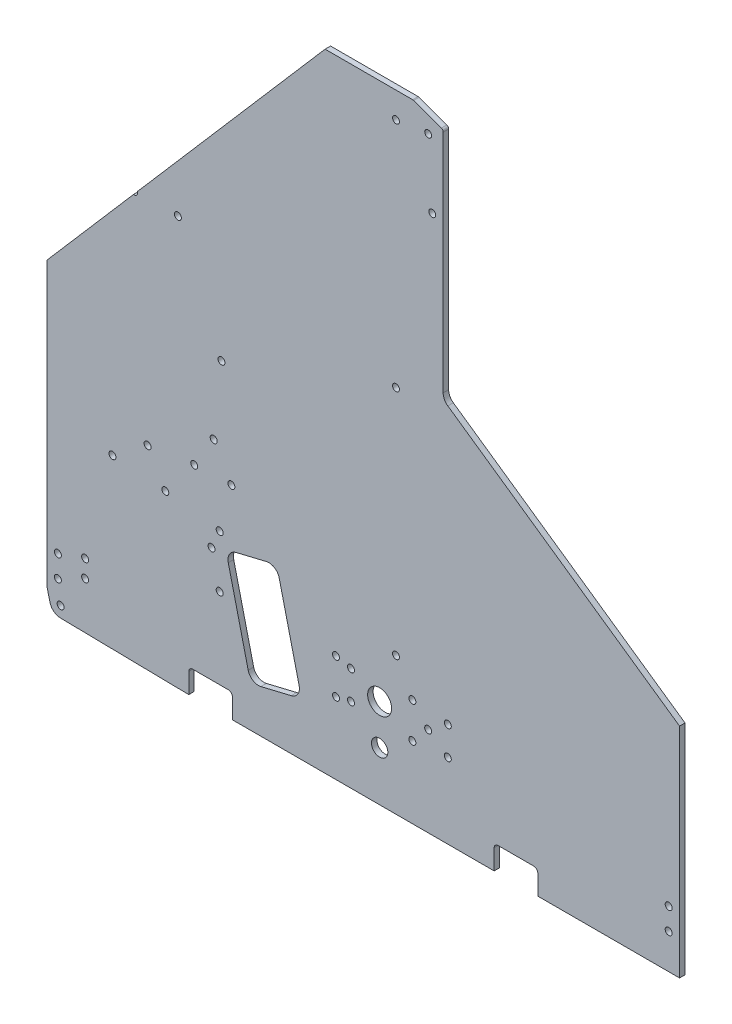
SolidWorks part; units mm, degrees
ref_plane "Front Plane" through (0, 0, 0) normal (0, 0, 1) x (1, 0, 0)
ref_plane "Top Plane" through (0, 0, 0) normal (0, 1, 0) x (1, 0, 0)
ref_plane "Right Plane" through (0, 0, 0) normal (1, 0, 0) x (0, 0, -1)
sketch "Sketch1" plane through (0, 0, 0) normal (0, 0, 1) x (1, 0, 0)
  line L0 (82.55, -20.32) -> (82.55, -6.35)
  line L2 (0, 0) -> (0, 157.48)
  line L4 (368.3, -20.32) -> (368.3, 106.68)
  line L5 (82.55, -6.35) -> (107.95, -6.35)
  line L6 (107.95, -6.35) -> (107.95, -20.32)
  line L7 (107.95, -20.32) -> (260.35, -20.32)
  line L8 (260.35, -20.32) -> (260.35, -6.35)
  line L9 (260.35, -6.35) -> (285.75, -6.35)
  line L10 (285.75, -6.35) -> (285.75, -20.32)
  line L11 (285.75, -20.32) -> (368.3, -20.32)
  line L12 (361.95, 12.7) -> (368.3, 12.7) construction
  line L13 (0, 0) -> (6.35, 0) construction
  line L14 (0.1896, -7.8901) -> (1.7771, -14.2401)
  line L15 (7.8295, -19.0491) -> (82.55, -20.32)
  line L16 (0, 0) -> (0, -6.35)
  line L17 (85.725, 97.155) -> (82.9754, 95.5675) construction
  line L18 (97.0634, 115.6163) -> (58.5686, 93.3913) construction
  line L19 (97.0634, 115.6163) -> (107.3822, 97.7437) construction
  line L20 (58.5686, 93.3913) -> (68.8873, 75.5187) construction
  line L21 (107.3822, 97.7437) -> (68.8873, 75.5187) construction
  line L22 (97.0634, 115.6163) -> (68.8873, 75.5187) construction
  line L23 (58.5686, 93.3913) -> (107.3822, 97.7437) construction
  line L24 (7.9375, -12.7) -> (95.7973, 60.4105) construction
  line L25 (203.2, 59.805) -> (203.2, 194.805) construction
  line L26 (203.2, 194.805) -> (203.2, 329.805) construction
  line L27 (355.6, 332.105) -> (330.2, 332.105) construction
  line L28 (330.2, 332.105) -> (330.2, 217.805) construction
  line L29 (330.2, 217.805) -> (355.6, 217.805) construction
  line L30 (355.6, 217.805) -> (355.6, 332.105) construction
  line L31 (203.2, 344.805) -> (203.2, 194.805) construction
  line L32 (50.8, 332.105) -> (76.2, 332.105) construction
  line L33 (76.2, 332.105) -> (76.2, 217.805) construction
  line L34 (50.8, 217.805) -> (50.8, 332.105) construction
  line L35 (76.2, 217.805) -> (50.8, 217.805) construction
  line L36 (213.2, 344.805) -> (230.6638, 338.455)
  line L37 (203.2, 344.805) -> (161.925, 344.805)
  line L38 (203.2, 344.805) -> (213.2, 344.805)
  line L39 (348.5362, 344.805) -> (413.4623, 344.805)
  line L40 (348.5362, 344.805) -> (230.6638, 344.805) construction
  line L42 (161.925, 344.805) -> (0, 157.48)
  line L44 (230.6638, 338.455) -> (230.6638, 202.565)
  line L45 (230.6638, 202.565) -> (368.3, 106.68)
  line L46 (213.2, 344.805) -> (-141.0713, 344.805) construction
  circle A0 centre (6.35, 0) radius 2.032
  circle A1 centre (6.35, 12.7) radius 2.032
  circle A2 centre (361.95, 0) radius 2.032
  circle A3 centre (361.95, 12.7) radius 2.032
  arc A5 (1.7771, -14.2401) -> (7.8295, -19.0491) centre (7.9375, -12.7) ccw
  circle A6 centre (7.9375, -12.7) radius 2.032
  arc A7 (0, -6.35) -> (0.1896, -7.8901) centre (6.35, -6.35) ccw
  circle A8 centre (38.1, 78.105) radius 2.032
  circle A9 centre (85.725, 97.155) radius 2.032
  circle A10 centre (58.5686, 93.3913) radius 2.032
  circle A11 centre (68.8873, 75.5187) radius 2.032
  circle A12 centre (107.3822, 97.7437) radius 2.032
  circle A13 centre (97.0634, 115.6163) radius 2.032
  circle A14 centre (95.7973, 60.4105) radius 2.032
  circle A15 centre (203.2, 59.805) radius 2
  circle A16 centre (203.2, 194.805) radius 2
  circle A17 centre (203.2, 329.805) radius 2
  circle A18 centre (63.5, 313.055) radius 2.032
  circle A19 centre (101.6, 157.48) radius 2.032
  circle A20 centre (355.6, 332.105) radius 2.032
  circle A21 centre (330.2, 332.105) radius 2.032
  circle A22 centre (355.6, 217.805) radius 2.032
  circle A23 centre (330.2, 217.805) radius 2.032
  circle A24 centre (50.8, 332.105) radius 2.032
  circle A25 centre (76.2, 332.105) radius 2.032
  circle A26 centre (50.8, 217.805) radius 2.032
  circle A27 centre (76.2, 217.805) radius 2.032
  circle A28 centre (221.9319, 332.105) radius 2
  circle A29 centre (224.3138, 293.243) radius 2.032
  point P82 (203.2, 344.805)
  point P83 (221.9319, 341.63)
  dimension "D6" = 4.064
  dimension "D10" = 6.35
  dimension "D11" = 4.064
  dimension "D17" = 38.1
  dimension "D27" = 4
  dimension "D31" = 4.064
  dimension "D32" = 41.275
  dimension "D36" = 4.064
  dimension "D47" = 45.212
  dimension "D48" = 4.064
  dimension "D2" = 127
  dimension "D3" = 13.97
  dimension "D4" = 25.4
  dimension "D5" = 152.4
  dimension "D7" = 12.7
  dimension "D8" = 6.35
  dimension "D9" = 20.32
  dimension "D12" = 12.7
  dimension "D13" = 1.5875
  dimension "D14" = 82.55
  dimension "D15" = 368.3
  dimension "D16" = 6.35
  dimension "D18" = 98.425
  dimension "D19" = 47.625
  dimension "D20" = 19.05
  dimension "D21" = 3.175
  dimension "D22" = 60
  dimension "D23" = 20.6375
  dimension "D24" = 44.45
  dimension "D25" = 38.1
  dimension "D26" = 114.3
  dimension "D28" = 135
  dimension "D29" = 12.7
  dimension "D30" = 15
  dimension "D33" = 63.5
  dimension "D34" = 27.4638
  dimension "D35" = 101.6
  dimension "D37" = 114.3
  dimension "D38" = 25.4
  dimension "D39" = 12.7
  dimension "D40" = 157.48
  dimension "D41" = 142.24
  dimension "D42" = 365.125
  dimension "D43" = 10
  dimension "D44" = 6.35
  dimension "D45" = 31.75
  dimension "D46" = 6.35
  dimension "D49" = 6.35
  dimension "D50" = 203.2
extrude "Boss-Extrude1" add sketch "Sketch1" along normal blind 3.175 contours L16 A7 L14 A5 L15 L2 A0 A1 A6 region at (171.4139, 119.6697, 0)
fillet "Fillet1" radius 2.286 4 edges at (285.75, -6.35, 1.5875) (107.95, -6.35, 1.5875) (260.35, -6.35, 1.5875) (82.55, -6.35, 1.5875)
fillet "Fillet2" radius 6.35 1 edges at (230.6638, 202.565, 1.5875)
sketch "Sketch2" plane through (0, 0, 0) normal (0, 0, -1) x (-1, 0, 0)
  circle A0 centre (-100.5528, 71.086) radius 2.032 construction
  circle A1 centre (-100.5528, 40.606) radius 2.032 construction
  circle A2 centre (-22.225, 18.2025) radius 2.032 construction
  circle A3 centre (-22.225, 8.0425) radius 2.032 construction
  circle A4 centre (-100.5528, 71.086) radius 2.032
  circle A5 centre (-100.5528, 40.606) radius 2.032
  circle A6 centre (-22.225, 18.2025) radius 2.032
  circle A7 centre (-22.225, 8.0425) radius 2.032
extrude "Cut-Extrude1" cut sketch "Sketch2" against normal through all
fillet "Fillet3" radius 1.5875 2 edges at (230.6638, 338.455, 1.5875) (213.2, 344.805, 1.5875)
sketch "Sketch3" plane through (0, 0, 3.175) normal (0, 0, 1) x (1, 0, 0)
  line L0 (132.9524, 63.2646) -> (132.7215, 64.2281) construction
  line L1 (128.3814, 66.8897) -> (110.6828, 62.6472) construction
  line L2 (114.5132, 58.4237) -> (126.8822, 61.3887) construction
  line L3 (108.0212, 58.3071) -> (108.2522, 57.3436) construction
  line L4 (131.2006, 57.703) -> (140.0164, 20.9265) construction
  line L5 (144.0993, 16.7636) -> (132.9524, 63.2646) construction
  line L6 (108.2522, 57.3436) -> (119.3991, 10.8426) construction
  line L7 (121.1509, 16.4042) -> (112.3351, 53.1807) construction
  line L8 (119.3991, 10.8426) -> (119.6301, 9.8791) construction
  line L9 (144.3303, 15.8001) -> (144.0993, 16.7636) construction
  line L10 (137.8383, 15.6835) -> (125.4694, 12.7185) construction
  line L11 (123.9701, 7.2175) -> (141.6687, 11.4601) construction
  line L12 (132.9524, 63.2646) -> (132.7215, 64.2281)
  line L13 (128.3814, 66.8897) -> (110.6828, 62.6472)
  line L14 (114.5132, 58.4237) -> (126.8822, 61.3887)
  line L15 (108.0212, 58.3071) -> (108.2522, 57.3436)
  line L16 (131.2006, 57.703) -> (140.0164, 20.9265)
  line L17 (144.0993, 16.7636) -> (132.9524, 63.2646)
  line L18 (108.2522, 57.3436) -> (119.3991, 10.8426)
  line L19 (121.1509, 16.4042) -> (112.3351, 53.1807)
  line L20 (119.3991, 10.8426) -> (119.6301, 9.8791)
  line L21 (144.3303, 15.8001) -> (144.0993, 16.7636)
  line L22 (137.8383, 15.6835) -> (125.4694, 12.7185)
  line L23 (123.9701, 7.2175) -> (141.6687, 11.4601)
  line L24 (127.7894, 69.3598) -> (110.0908, 65.1172)
  line L25 (105.5512, 57.715) -> (105.7822, 56.7515)
  line L26 (105.7822, 56.7515) -> (116.9291, 10.2505)
  line L27 (116.9291, 10.2505) -> (117.16, 9.287)
  line L28 (124.5622, 4.7475) -> (142.2608, 8.99)
  line L29 (146.8003, 16.3922) -> (146.5694, 17.3557)
  line L30 (146.5694, 17.3557) -> (135.4225, 63.8567)
  line L31 (135.4225, 63.8567) -> (135.1915, 64.8202)
  arc A0 (132.7215, 64.2281) -> (128.6308, 66.9403) centre (129.2206, 63.3889) ccw construction
  arc A1 (110.6828, 62.6472) -> (110.4377, 62.5791) centre (111.522, 59.1463) ccw construction
  arc A2 (128.6308, 66.9403) -> (128.3814, 66.8897) centre (129.2206, 63.3889) ccw construction
  arc A3 (110.4377, 62.5791) -> (108.0212, 58.3071) centre (111.522, 59.1463) ccw construction
  arc A4 (119.6301, 9.8791) -> (123.7207, 7.1669) centre (123.1309, 10.7183) ccw construction
  arc A5 (141.9139, 11.5281) -> (144.3303, 15.8001) centre (140.8295, 14.9609) ccw construction
  arc A6 (141.6687, 11.4601) -> (141.9139, 11.5281) centre (140.8295, 14.9609) ccw construction
  arc A7 (123.7207, 7.1669) -> (123.9701, 7.2175) centre (123.1309, 10.7183) ccw construction
  arc A8 (132.7215, 64.2281) -> (128.6308, 66.9403) centre (129.2206, 63.3889) ccw
  arc A9 (110.6828, 62.6472) -> (110.4377, 62.5791) centre (111.522, 59.1463) ccw
  arc A10 (128.6308, 66.9403) -> (128.3814, 66.8897) centre (129.2206, 63.3889) ccw
  arc A11 (110.4377, 62.5791) -> (108.0212, 58.3071) centre (111.522, 59.1463) ccw
  arc A12 (119.6301, 9.8791) -> (123.7207, 7.1669) centre (123.1309, 10.7183) ccw
  arc A13 (141.9139, 11.5281) -> (144.3303, 15.8001) centre (140.8295, 14.9609) ccw
  arc A14 (141.6687, 11.4601) -> (141.9139, 11.5281) centre (140.8295, 14.9609) ccw
  arc A15 (123.7207, 7.1669) -> (123.9701, 7.2175) centre (123.1309, 10.7183) ccw
  arc A16 (110.0908, 65.1172) -> (109.6726, 65.0012) centre (111.522, 59.1463) ccw
  arc A17 (109.6726, 65.0012) -> (105.5512, 57.715) centre (111.522, 59.1463) ccw
  arc A18 (117.16, 9.287) -> (124.1369, 4.6613) centre (123.1309, 10.7183) ccw
  arc A19 (124.1369, 4.6613) -> (124.5622, 4.7475) centre (123.1309, 10.7183) ccw
  arc A20 (142.2608, 8.99) -> (142.6789, 9.1061) centre (140.8295, 14.9609) ccw
  arc A21 (142.6789, 9.1061) -> (146.8003, 16.3922) centre (140.8295, 14.9609) ccw
  arc A22 (135.1915, 64.8202) -> (128.2147, 69.446) centre (129.2206, 63.3889) ccw
  arc A23 (128.2147, 69.446) -> (127.7894, 69.3598) centre (129.2206, 63.3889) ccw
  ellipse E0 centre (124.5974, 48.8487) end of major axis (128.5376, 61.3578) minor radius 6 (131.2006, 57.703) -> (126.8822, 61.3887) ccw construction
  ellipse E1 centre (122.2349, 48.2824) end of major axis (113.0518, 57.6456) minor radius 6 (114.5132, 58.4237) -> (112.3351, 53.1807) ccw construction
  ellipse E2 centre (127.7541, 25.2585) end of major axis (131.6942, 37.7675) minor radius 6 (121.1509, 16.4042) -> (125.4694, 12.7185) ccw construction
  ellipse E3 centre (130.1166, 25.8248) end of major axis (139.2998, 16.4616) minor radius 6 (137.8383, 15.6835) -> (140.0164, 20.9265) ccw construction
  ellipse E4 centre (124.5974, 48.8487) end of major axis (120.6573, 36.3397) minor radius 6 (131.2006, 57.703) -> (126.8822, 61.3887) ccw
  ellipse E5 centre (122.2349, 48.2824) end of major axis (131.4181, 38.9192) minor radius 6 (114.5132, 58.4237) -> (112.3351, 53.1807) ccw
  ellipse E6 centre (127.7541, 25.2585) end of major axis (131.6942, 37.7675) minor radius 6 (121.1509, 16.4042) -> (125.4694, 12.7185) ccw
  ellipse E7 centre (130.1166, 25.8248) end of major axis (139.2998, 16.4616) minor radius 6 (137.8383, 15.6835) -> (140.0164, 20.9265) ccw
  dimension "D1" = 2.54
extrude "Cut-Extrude2" cut sketch "Sketch3" against normal through all contours A22 A23 L24 A16 A17 L25 L26 L27 A18 A19 L28 A20 A21 L29 L30 L31 A15 A12 L20 L18 L15 A11 A9 L13 A10 A8 L12 L17 L21 A13 A14 L23 | A12 A15 L23 A14 A13 L21 L17 L12 A8 A10 L13 A9 A11 L15 L18 L20 E7 L22 E6 L19 E5 L14 E4 L16 | L22 E7 L16 E4 L14 E5 L19 E6 region at (137.844, 39.8506, 3.175) region at (126.1758, 37.0536, 3.175) region at (128.1544, 68.6507, 3.175)
sketch "Sketch4" plane through (0, 0, 3.175) normal (0, 0, 1) x (1, 0, 0)
  line L0 (107.3822, 97.7437) -> (68.8873, 75.5187) construction
  line L1 (168.275, 21.4312) -> (212.725, 21.4312) construction
  line L2 (168.275, 21.4312) -> (168.275, 42.0687) construction
  line L3 (168.275, 42.0687) -> (212.725, 42.0687) construction
  line L4 (212.725, 21.4312) -> (212.725, 42.0687) construction
  line L5 (168.275, 21.4312) -> (212.725, 42.0687) construction
  line L6 (168.275, 42.0687) -> (212.725, 21.4312) construction
  line L7 (97.0634, 115.6163) -> (107.3822, 97.7437) construction
  line L8 (107.95, -20.32) -> (260.35, -20.32) construction
  line L9 (193.675, 31.75) -> (177.005, 31.75) construction
  line L10 (190.5, 31.75) -> (193.675, 31.75) construction
  line L11 (6.35, 12.7) -> (361.95, 12.7) construction
  line L12 (107.95, -6.35) -> (107.95, -20.32) construction
  line L13 (193.675, 31.75) -> (220.6625, 31.75) construction
  line L14 (177.005, 23.4569) -> (177.005, 40.0431) construction
  line L15 (213.2, 44.805) -> (193.2, 44.805) construction
  line L16 (213.2, 44.805) -> (213.2, 344.805) construction
  line L17 (213.2, 344.805) -> (193.2, 344.805) construction
  line L18 (193.2, 44.805) -> (193.2, 344.805) construction
  line L19 (213.2, 44.805) -> (193.2, 344.805) construction
  line L20 (213.2, 344.805) -> (193.2, 44.805) construction
  line L21 (226.9319, 332.105) -> (226.9319, 31.75) construction
  line L22 (237.33, 40.0431) -> (233.3612, 40.0431) construction
  line L23 (237.33, 23.4569) -> (233.3612, 23.4569) construction
  circle A0 centre (168.275, 42.0687) radius 2.032
  circle A1 centre (212.725, 42.0687) radius 2.032
  circle A2 centre (212.725, 21.4312) radius 2.032
  circle A3 centre (168.275, 21.4312) radius 2.032
  circle A4 centre (193.675, 31.75) radius 6.985
  circle A7 centre (220.6625, 31.75) radius 14.2875 construction
  circle A8 centre (193.675, 31.75) radius 12.7 construction
  circle A9 centre (177.005, 40.0431) radius 2.032
  circle A10 centre (177.005, 23.4569) radius 2.032
  circle A11 centre (237.33, 40.0431) radius 2.032 construction
  circle A12 centre (237.33, 23.4569) radius 2.032 construction
  circle A13 centre (193.675, 8.4667) radius 4.7625
  circle A14 centre (221.9319, 31.75) radius 2.032
  circle A15 centre (221.9319, 31.75) radius 5 construction
  circle A16 centre (221.9319, 332.105) radius 5 construction
  circle A17 centre (233.3612, 23.4569) radius 2.032
  circle A18 centre (233.3612, 40.0431) radius 2.032
  point P0 (190.5, 31.75)
  point P26 (203.2, 194.805)
  point P38 (177.005, 31.75)
  dimension "D1" = 4.064
  dimension "D4" = 13.97
  dimension "D7" = 9.525
  dimension "D10" = 25.4
  dimension "D11" = 28.575
  dimension "D16" = 10
  dimension "D17" = 4.064
  dimension "D18" = 10
  dimension "D2" = 52.07
  dimension "D3" = 3.175
  dimension "D5" = 82.55
  dimension "D6" = 26.9875
  dimension "D8" = 20
  dimension "D9" = 300
  dimension "D12" = 16.67
  dimension "D13" = 16.5862
  dimension "D14" = 60.325
  dimension "D15" = 23.2833
  dimension "D19" = 3.9688
extrude "Cut-Extrude3" cut sketch "Sketch4" against normal through all
